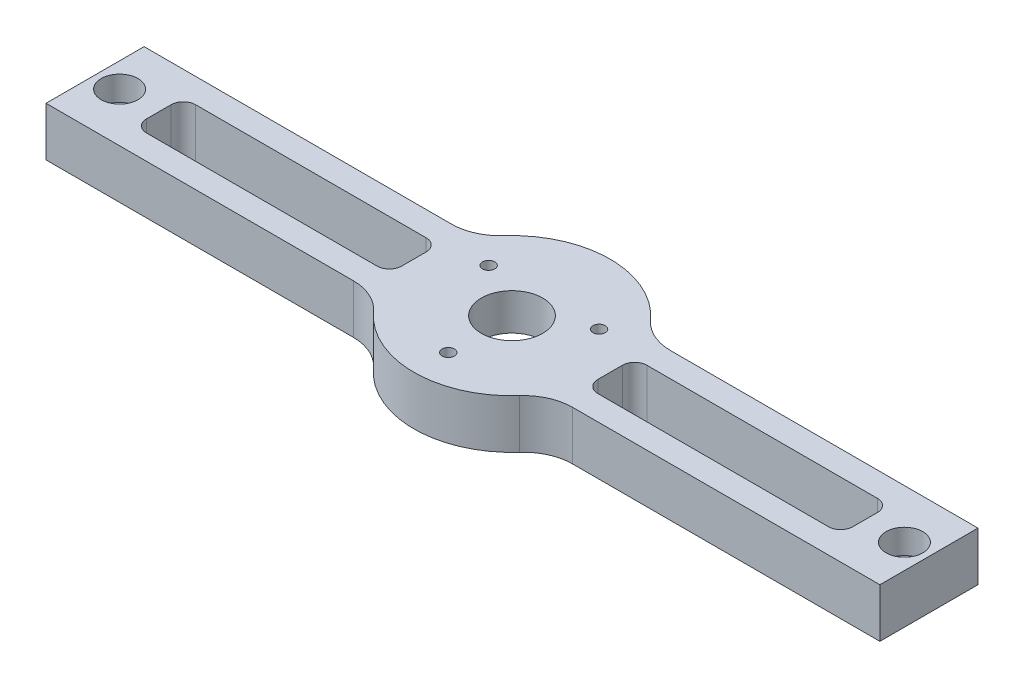
SolidWorks part; units mm, degrees
material "6061-T6 (SS)"
ref_plane "Front Plane" through (0, 0, 0) normal (0, 0, 1) x (1, 0, 0)
ref_plane "Top Plane" through (0, 0, 0) normal (0, 1, 0) x (1, 0, 0)
ref_plane "Right Plane" through (0, 0, 0) normal (1, 0, 0) x (0, 0, -1)
sketch "Sketch2" plane through (0, 0, 0) normal (0, 1, 0) x (1, 0, 0)
  line L0 (-21.997, 0) -> (0, 0) construction
  line L1 (-107.95, -25.4) -> (-21.997, -25.4)
  line L2 (-107.95, -25.4) -> (-107.95, 0)
  line L3 (-107.95, 0) -> (-21.997, 0)
  line L4 (-21.997, -25.4) -> (-21.997, 0)
  line L5 (21.997, -25.4) -> (107.95, -25.4)
  line L6 (21.997, -25.4) -> (21.997, 0)
  line L7 (21.997, 0) -> (107.95, 0)
  line L8 (107.95, -25.4) -> (107.95, 0)
  line L9 (0, 0) -> (21.997, 0) construction
  circle A0 centre (0, -12.7) radius 7.9375
  circle A1 centre (0, -12.7) radius 25.4
  point P13 (107.95, -12.7)
  dimension "D3" = 215.9
  dimension "D4" = 15.875
  dimension "D5" = 50.8
  dimension "D1" = 25.4
  dimension "D2" = 25.4
extrude "Boss-Extrude1" add sketch "Sketch2" along normal blind 12.7 contours A1 L3 L2 L1 | L4 A1 | L6 A1 L4 A0 | L6 A1 | A1 L5 L8 L7 region at (-66.1179, 0, 12.7) region at (-23.3664, 0, 12.7) region at (-21.325, 0, 12.7) region at (66.1179, 0, 12.7) region at (23.3664, 0, 12.7)
fillet "Fillet1" radius 12.7 4 edges at (21.997, 6.35, 0) (21.997, 6.35, 25.4) (-21.997, 6.35, 25.4) (-21.997, 6.35, 0)
sketch "Sketch3" plane through (0, 0, 0) normal (0, -1, 0) x (1, 0, 0)
  circle A0 centre (0, 12.7) radius 22.225
  dimension "D1" = 44.45
extrude "Cut-Extrude1" cut sketch "Sketch3" against normal blind 3.175
sketch "Sketch4" plane through (0, 12.7, 0) normal (0, 1, 0) x (1, 0, 0)
  line L0 (-107.95, -25.4) -> (-107.95, 0) construction
  line L1 (107.95, -25.4) -> (107.95, 0) construction
  circle A0 centre (-101.6, -12.7) radius 4.7625
  circle A1 centre (101.6, -12.7) radius 4.7625
  point P4 (-107.95, -12.7)
  point P5 (107.95, -12.7)
  dimension "D1" = 9.525
  dimension "D2" = 9.525
  dimension "D3" = 6.35
  dimension "D4" = 6.35
extrude "Cut-Extrude2" cut sketch "Sketch4" against normal blind 6.35
sketch "Sketch5" plane through (0, 6.35, 0) normal (0, 1, 0) x (1, 0, 0)
  circle A0 centre (-101.6, -12.7) radius 3.175
  circle A1 centre (101.6, -12.7) radius 3.175
  dimension "D1" = 6.35
  dimension "D2" = 6.35
extrude "Cut-Extrude3" cut sketch "Sketch5" against normal through all
sketch "Sketch6" plane through (0, 3.175, 0) normal (0, -1, 0) x (1, 0, 0)
  circle A0 centre (0, 29.21) radius 1.5875
  circle A1 centre (0, 12.7) radius 7.9375 construction
  circle A2 centre (0, 12.7) radius 7.9375 construction
  circle A3 centre (14.2981, 4.445) radius 1.5875
  circle A4 centre (-14.2981, 4.445) radius 1.5875
  dimension "D2" = 3.175
  dimension "D1" = 16.51
  dimension "D3" = 3
extrude "Cut-Extrude4" cut sketch "Sketch6" against normal through all
sketch "Sketch7" plane through (0, 12.7, 0) normal (0, 1, 0) x (1, 0, 0)
  line L0 (-107.95, 0) -> (-28.3981, 0) construction
  line L1 (-91.44, -19.05) -> (-25.4, -19.05)
  line L2 (-91.44, -19.05) -> (-91.44, -6.35)
  line L3 (-91.44, -6.35) -> (-25.4, -6.35)
  line L4 (-25.4, -19.05) -> (-25.4, -6.35)
  line L5 (25.4, -19.05) -> (91.44, -19.05)
  line L6 (25.4, -19.05) -> (25.4, -6.35)
  line L7 (25.4, -6.35) -> (91.44, -6.35)
  line L8 (91.44, -19.05) -> (91.44, -6.35)
  line L9 (-107.95, -25.4) -> (-28.3981, -25.4) construction
  circle A0 centre (-101.6, -12.7) radius 4.7625 construction
  circle A1 centre (101.6, -12.7) radius 4.7625 construction
  dimension "D3" = 10.16
  dimension "D1" = 6.35
  dimension "D2" = 6.35
  dimension "D4" = 50.8
  dimension "D5" = 10.16
extrude "Cut-Extrude5" cut sketch "Sketch7" against normal through all
fillet "Fillet2" radius 3.175 8 edges at (25.4, 6.35, 6.35) (25.4, 6.35, 19.05) (91.44, 6.35, 19.05) (91.44, 6.35, 6.35) (-25.4, 6.35, 6.35) (-25.4, 6.35, 19.05) (-91.44, 6.35, 19.05) (-91.44, 6.35, 6.35)
